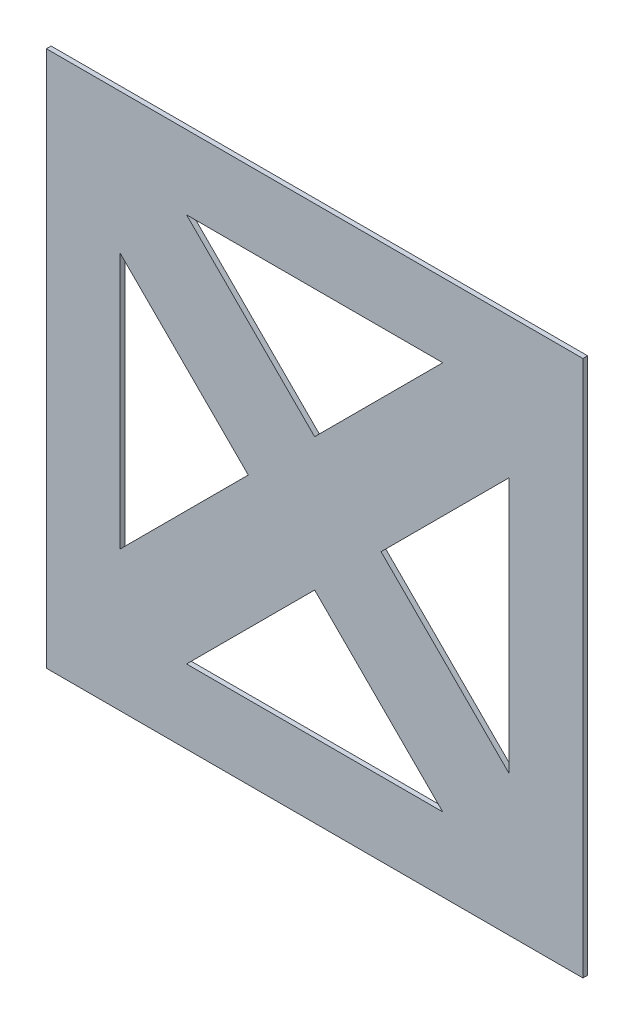
SolidWorks part; units mm, degrees
material "3.0205 (EN-AW 1200)"
ref_plane "Piano frontale" through (0, 0, 0) normal (0, 0, 1) x (1, 0, 0)
ref_plane "Piano superiore" through (0, 0, 0) normal (0, 1, 0) x (1, 0, 0)
ref_plane "Piano destro" through (0, 0, 0) normal (1, 0, 0) x (0, 0, -1)
sketch "Schizzo1" plane through (0, 0, 0) normal (0, 0, 1) x (1, 0, 0)
  line L1 (-400, -400) -> (400, -400)
  line L2 (-400, -400) -> (-400, 400)
  line L3 (-400, 400) -> (400, 400)
  line L4 (400, -400) -> (400, 400)
  line L5 (-400, -400) -> (400, 400) construction
  line L6 (-400, 400) -> (400, -400) construction
  point P0 (0, 0)
  dimension "D1" = 800
  dimension "D2" = 800
extrude "Estrusione-Estrusione1" add sketch "Schizzo1" along normal blind 7
sketch "Schizzo3" plane through (0, 0, 7) normal (0, 0, 1) x (1, 0, 0)
  line L0 (-400, 400) -> (400, -400) construction
  line L1 (-400, -400) -> (400, 400) construction
  line L2 (-191.0051, 290) -> (0, 98.9949)
  line L3 (0, 98.9949) -> (191.0051, 290)
  line L4 (191.0051, 290) -> (-191.0051, 290)
  line L5 (400, 400) -> (-400, 400) construction
  line L6 (-98.9949, 0) -> (-290, 191.0051)
  line L7 (-290, 191.0051) -> (-290, -191.0051)
  line L8 (-290, -191.0051) -> (-98.9949, 0)
  line L9 (290, -191.0051) -> (98.9949, 0)
  line L10 (98.9949, 0) -> (290, 191.0051)
  line L11 (290, 191.0051) -> (290, -191.0051)
  line L12 (191.0051, -290) -> (0, -98.9949)
  line L13 (0, -98.9949) -> (-191.0051, -290)
  line L14 (-191.0051, -290) -> (191.0051, -290)
  line L15 (0, 98.9949) -> (0, -98.9949) construction
  line L16 (-98.9949, 0) -> (98.9949, 0) construction
  line L17 (-400, -400) -> (400, -400) construction
  line L20 (-191.0051, 290) -> (-290, 191.0051) construction
  line L21 (98.9949, 0) -> (0, -98.9949) construction
  line L22 (191.0051, 290) -> (290, 191.0051) construction
  line L23 (-98.9949, 0) -> (0, -98.9949) construction
  dimension "D1" = 140
  dimension "D2" = 140
  dimension "D3" = 110
  dimension "D4" = 70
  dimension "D5" = 110
extrude "Taglio-Estrusione2" cut sketch "Schizzo3" against normal through all
